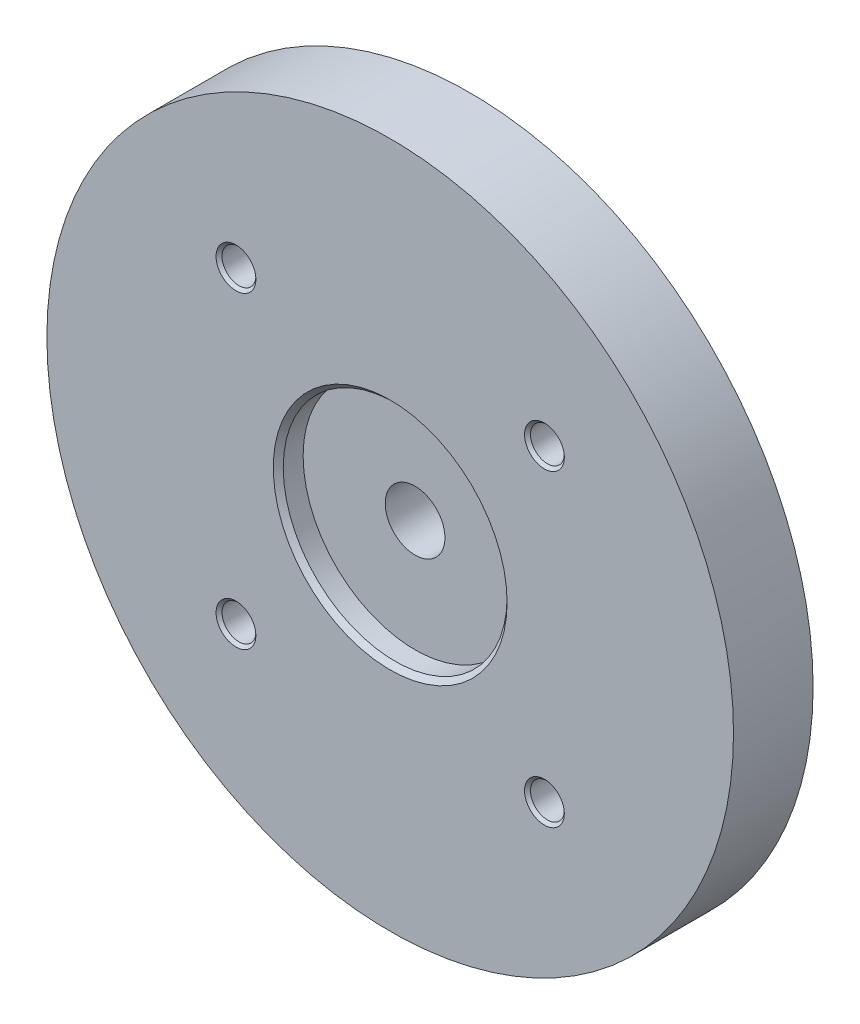
SolidWorks part; units mm, degrees
ref_plane "Front Plane" through (0, 0, 0) normal (0, 0, 1) x (1, 0, 0)
ref_plane "Top Plane" through (0, 0, 0) normal (0, 1, 0) x (1, 0, 0)
ref_plane "Right Plane" through (0, 0, 0) normal (1, 0, 0) x (0, 0, -1)
sketch "Sketch2" plane through (0, 0, 0) normal (0, 0, 1) x (1, 0, 0)
  circle A0 centre (0, 0) radius 34.5
  dimension "D1" = 69
extrude "Boss-Extrude1" add sketch "Sketch2" along normal blind 8
sketch "Sketch6" plane through (0, 0, 0) normal (0, 0, -1) x (-1, 0, 0)
  circle A0 centre (0, 0) radius 10
  dimension "D1" = 20
extrude "Boss-Extrude2" add sketch "Sketch6" along normal blind 2
sketch "Sketch3" plane through (0, 0, 8) normal (0, 0, 1) x (1, 0, 0)
  line L0 (0, -15.5) -> (0, 15.5) construction
  line L1 (15.5, 15.5) -> (-15.5, 15.5) construction
  line L2 (15.5, -15.5) -> (-15.5, -15.5) construction
  circle A0 centre (-15.5, 15.5) radius 1.7
  circle A1 centre (15.5, 15.5) radius 1.7
  circle A2 centre (15.5, -15.5) radius 1.7
  circle A3 centre (-15.5, -15.5) radius 1.7
  circle A4 centre (0, 0) radius 3
  point P12 (0, 0)
  point P16 (0, 15.5)
  point P19 (0, -15.5)
  dimension "D1" = 3.4
  dimension "D2" = 3.4
  dimension "D3" = 3.4
  dimension "D4" = 3.4
  dimension "D8" = 6
  dimension "D5" = 31
  dimension "D6" = 31
  dimension "D7" = 31
extrude "Cut-Extrude1" cut sketch "Sketch3" against normal through all both and the other way through all
sketch "Sketch4" plane through (0, 0, 0) normal (0, 0, -1) x (-1, 0, 0)
  circle A0 centre (-15.5, 15.5) radius 2.8
  circle A1 centre (15.5, 15.5) radius 2.8
  circle A2 centre (15.5, -15.5) radius 2.8
  circle A3 centre (-15.5, -15.5) radius 2.8
  dimension "D1" = 5.6
  dimension "D2" = 5.6
  dimension "D3" = 5.6
  dimension "D4" = 5.6
extrude "Cut-Extrude2" cut sketch "Sketch4" against normal blind 3 and the other way through all
sketch "Sketch5" plane through (0, 0, 0) normal (0, 0, -1) x (-1, 0, 0)
  circle A0 centre (0, 30) radius 2.1
  circle A1 centre (30, 0) radius 2.1
  circle A2 centre (0, -30) radius 2.1
  circle A3 centre (-30, 0) radius 2.1
  circle A4 centre (0, 0) radius 30 construction
  dimension "D1" = 4.2
  dimension "D2" = 60
  dimension "D3" = 4
extrude "Cut-Extrude3" cut sketch "Sketch5" against normal blind 6
fillet "Fillet1" radius 1 1 edges at (-10, 0, 0)
sketch "Sketch7" plane through (0, 0, 8) normal (0, 0, 1) x (1, 0, 0)
  circle A0 centre (0, 0) radius 11.25
  dimension "D1" = 22.5
extrude "Cut-Extrude4" cut sketch "Sketch7" against normal blind 2.5
chamfer "Chamfer1" distance 0.5 angle 45 1 edges at (11.25, 0, 8)
chamfer "Chamfer2" distance 0.3 angle 45 4 edges at (-13.8, -15.5, 8) (17.2, -15.5, 8) (17.2, 15.5, 8) (-13.8, 15.5, 8)
equation "\"N_pins\"= 26"
equation "\"N_lobes\"= \"N_pins\" - 1"
equation "\"R_pc\"= 25"
equation "\"D_pin\"= 3"
equation "\"R_pin\"= \"D_pin\" / 2"
equation "\"ecc\"= 0.72"
equation "\"t_disc\"= 7"
equation "\"N_out\"= 8"
equation "\"D_outc\"=22"
equation "\"D_roller\"= 5"
equation "\"D_outhole\"= \"D_roller\" + 2 * \"ecc\""
equation "\"D_cam_OD\"= 21"
equation "\"D_cam_ID\"= 10"
equation "\"clr_bore\"= 1"
equation "\"D_bore\"= 2 * \"R_pc\" + \"clr_bore\""
equation "\"t_wall\"= 7.5"
equation "\"D_housing\"= 69"
equation "\"D1@Sketch2\"=\"D_housing\""
